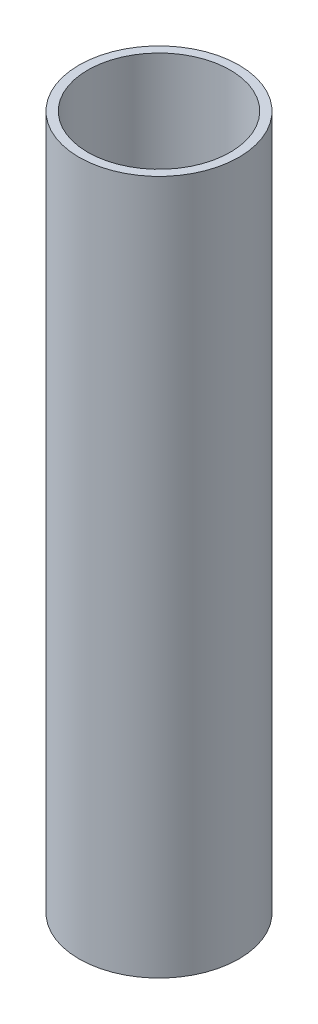
SolidWorks part; units mm, degrees
material "Epoxy, Unfilled"
ref_plane "Front Plane" through (0, 0, 0) normal (0, 0, 1) x (1, 0, 0)
ref_plane "Top Plane" through (0, 0, 0) normal (0, 1, 0) x (1, 0, 0)
ref_plane "Right Plane" through (0, 0, 0) normal (1, 0, 0) x (0, 0, -1)
sketch "Sketch2" plane through (0, 0, 0) normal (0, 1, 0) x (1, 0, 0)
  circle A0 centre (0, 0) radius 58.4835
  circle A1 centre (0, 0) radius 52.1335
extrude "Boss-Extrude1" add sketch "Sketch2" along normal blind 508
